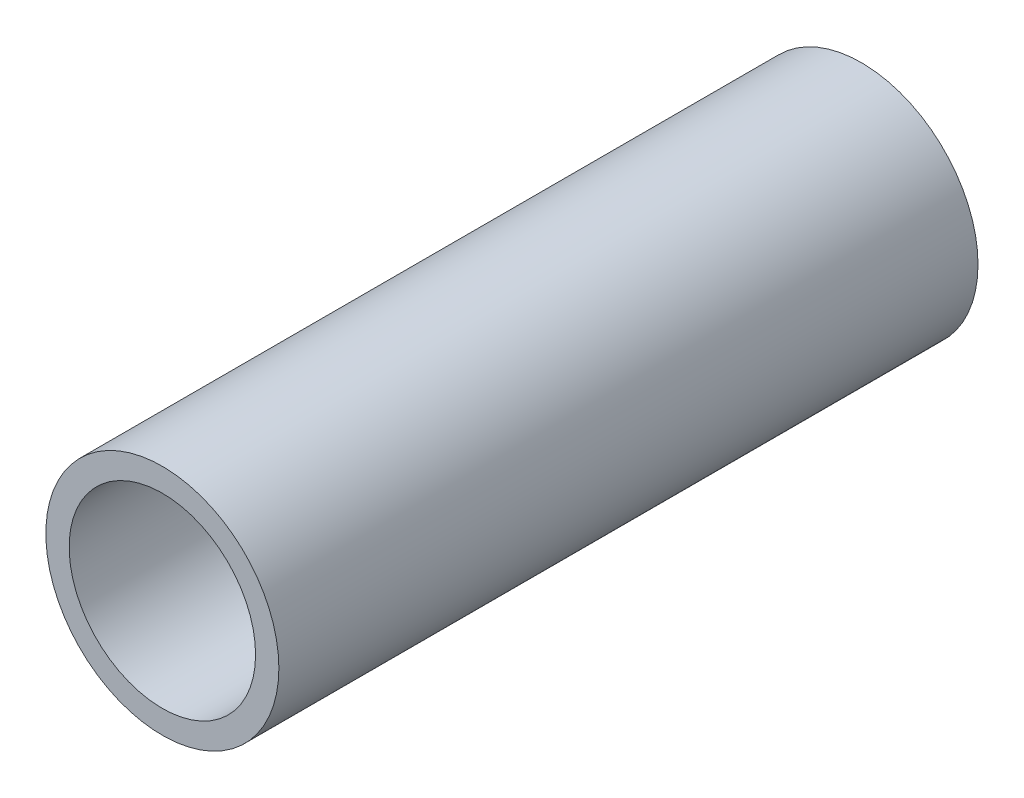
SolidWorks part; units mm, degrees
ref_plane "Front Plane" through (0, 0, 0) normal (0, 0, 1) x (1, 0, 0)
ref_plane "Top Plane" through (0, 0, 0) normal (0, 1, 0) x (1, 0, 0)
ref_plane "Right Plane" through (0, 0, 0) normal (1, 0, 0) x (0, 0, -1)
sketch "Sketch1" plane through (0, 0, 0) normal (0, 0, 1) x (1, 0, 0)
  circle A0 centre (0, 0) radius 25
  circle A1 centre (0, 0) radius 20
  dimension "D1" = 50
  dimension "D2" = 5
extrude "Boss-Extrude1" add sketch "Sketch1" along normal blind 150
ref_plane "Plane1" through (0, -25, 0) normal (0, -1, 0) x (-1, 0, 0)
ref_axis "Axis2" through (0, 0, 150) along (0, 0, -1)
